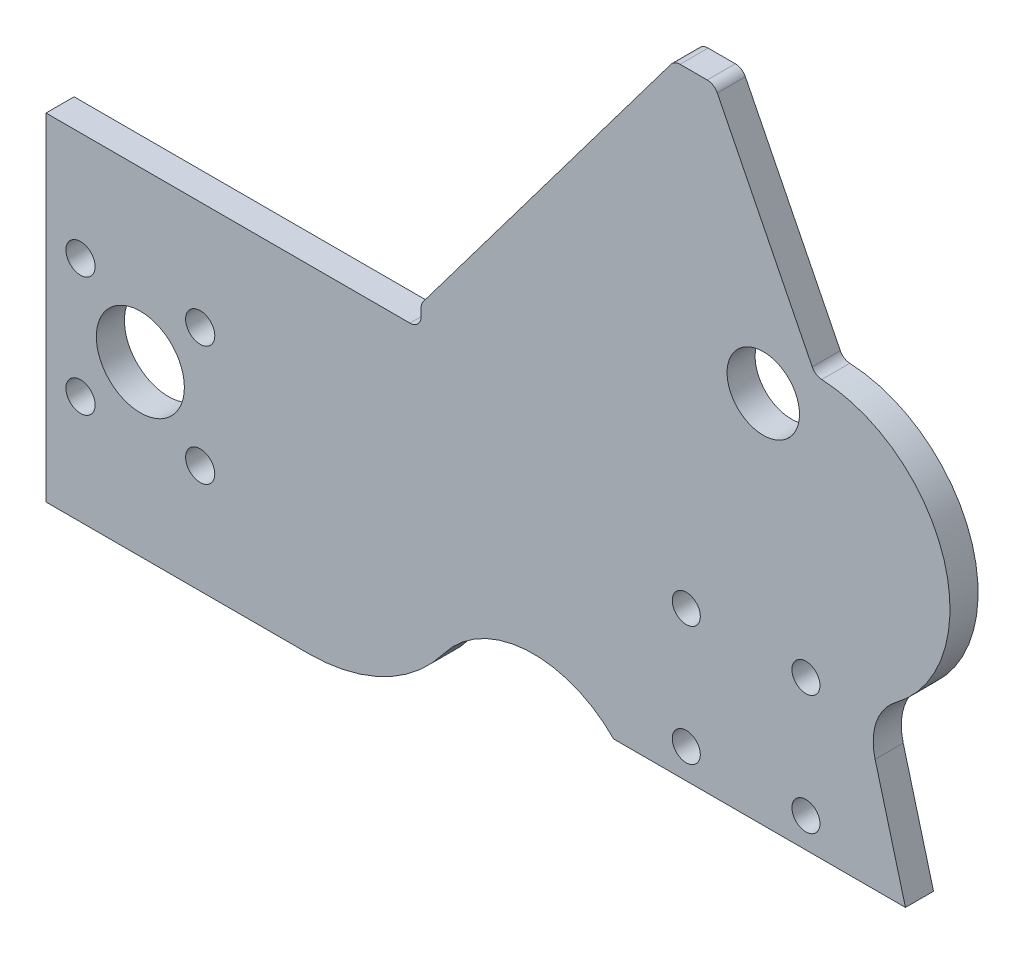
SolidWorks part; units mm, degrees
ref_plane "Front Plane" through (0, 0, 0) normal (0, 0, 1) x (1, 0, 0)
ref_plane "Top Plane" through (0, 0, 0) normal (0, 1, 0) x (1, 0, 0)
ref_plane "Right Plane" through (0, 0, 0) normal (1, 0, 0) x (0, 0, -1)
sketch "Sketch1" plane through (0, 0, 0) normal (0, 0, 1) x (1, 0, 0)
  line L0 (0, 0) -> (107.95, 0)
  line L3 (0, 38.1) -> (0, 25.4)
  line L4 (95.3675, 55.88) -> (0, 38.1)
  line L5 (0, 19.05) -> (100.2273, 19.05) construction
  line L6 (19.05, 19.05) -> (19.05, 28.62) construction
  line L7 (19.05, 19.05) -> (25.817, 25.817) construction
  line L8 (107.95, 0) -> (100.9363, 26.1756)
  line L10 (0, 12.7) -> (0, 0)
  line L11 (0, 25.4) -> (-7.62, 25.4)
  line L13 (0, 12.7) -> (-7.62, 12.7)
  line L14 (-7.62, 25.4) -> (-7.62, 12.7)
  line L15 (100.9363, 26.1756) -> (100.8688, 26.4276)
  arc A0 (100.8688, 26.4276) -> (95.3675, 55.88) centre (95.3675, 40.64) ccw
  circle A1 centre (95.3675, 40.64) radius 4.0957 construction
  circle A2 centre (19.05, 19.05) radius 9.57 construction
  circle A3 centre (25.817, 25.817) radius 1.651
  circle A4 centre (25.817, 12.283) radius 1.651
  circle A7 centre (12.283, 12.283) radius 1.651 [skipped]
  circle A8 centre (12.283, 25.817) radius 1.651 [skipped]
  point P26 (19.05, 19.05)
  dimension "D1" = 8.1915
  dimension "D5" = 15.24
  dimension "D4" = 19.14
  dimension "D7" = 3.302
  dimension "D11" = 97.0107
  dimension "D2" = 38.1
  dimension "D3" = 40.64
  dimension "D6" = 107.95
  dimension "D8" = 45
  dimension "D9" = 4
  dimension "D10" = 19.05
  dimension "D12" = 75
  dimension "D14" = 12.7
  dimension "D15" = 12.7
  dimension "D16" = 7.62
extrude "Boss-Extrude1" add sketch "Sketch1" along normal blind 3.175
sketch "Sketch2" plane through (0, 0, 3.175) normal (0, 0, 1) x (1, 0, 0)
  circle A0 centre (95.3675, 40.64) radius 38.1 construction
  point P3 (0, 0)
sketch "Sketch6" plane through (0, 0, 3.175) normal (0, 0, 1) x (1, 0, 0)
  line L0 (0, 0) -> (107.95, 0) construction
  line L1 (50.8, 0) -> (76.2, 0)
  arc A0 (76.2, 0) -> (50.8, 0) centre (63.5, 0) ccw
  dimension "D1" = 25.4
  dimension "D2" = 31.75
extrude "Cut-Extrude2" cut sketch "Sketch6" against normal blind 6.35
sketch "Sketch7" plane through (0, 0, 3.175) normal (0, 0, 1) x (1, 0, 0)
  line L0 (12.283, 25.817) -> (25.817, 12.283) construction
  line L1 (12.283, 12.283) -> (25.817, 25.817) construction
  circle A0 centre (19.05, 19.05) radius 4.9784
  circle A2 centre (80.7829, 12.2536) radius 1.5875
  circle A3 centre (94.316, 12.2536) radius 1.5875
  circle A4 centre (80.7829, 25.7876) radius 1.5875
  circle A5 centre (94.316, 25.7876) radius 1.5875
  point P10 (0, 0)
  point P11 (0, 0)
  point P20 (0, 0)
  dimension "D1" = 9.9568
extrude "Cut-Extrude3" cut sketch "Sketch7" against normal through all
fillet "Fillet1" radius 6.35 1 edges at (100.8688, 26.4276, 1.5875)
sketch "Sketch8" plane through (0, 0, 3.175) normal (0, 0, 1) x (1, 0, 0)
  line L1 (0, 38.1) -> (50.8, 38.1)
  line L2 (0, 38.1) -> (0, 50.8)
  line L3 (0, 50.8) -> (50.8, 50.8)
  line L4 (50.8, 38.1) -> (50.8, 50.8)
  dimension "D1" = 50.8
  dimension "D2" = 12.7
extrude "Cut-Extrude4" cut sketch "Sketch8" against normal blind 50.8
sketch "Sketch9" plane through (0, 0, 3.175) normal (0, 0, 1) x (1, 0, 0)
  line L3 (50.8, 40.64) -> (57.15, 40.64)
  line L5 (57.15, 40.64) -> (50.8, 40.64)
  line L6 (57.15, 40.64) -> (57.15, 50.8)
  line L7 (57.15, 50.8) -> (50.8, 50.8)
  line L8 (50.8, 40.64) -> (50.8, 50.8)
  line L9 (0, 38.1) -> (50.8, 38.1) construction
  line M8 (50.8, 47.571) -> (50.8, 38.1)
  line M21 (95.3675, 55.88) -> (50.8, 47.571)
  dimension "D1" = 10.16
  dimension "D2" = 2.54
  dimension "D3" = 6.35
extrude "Cut-Extrude5" cut sketch "Sketch9" against normal blind 19.304 contours L3 L6 M21 M8 region at (54.0583, 44.4092, 3.175)
fillet "Fillet6" radius 6.35 1 edges at (57.15, 40.64, 1.5875)
fillet "Fillet7" radius 6.35 1 edges at (57.15, 48.7549, 1.5875)
fillet "Fillet8" radius 19.05 1 edges at (50.8, 0, 1.5875)
sketch "Sketch12" plane through (0, 0, 3.175) normal (0, 0, 1) x (1, 0, 0)
  line L0 (107.95, 0) -> (146.812, 0) construction
  line L1 (8.0257, 45.4128) -> (80.6683, 75.7903) construction
  line L2 (95.3675, 40.64) -> (80.6683, 75.7903) construction
  line L3 (80.6683, 75.7903) -> (79.4434, 78.7195) construction
  line L4 (50.8, 40.64) -> (85.0271, 40.64)
  line L5 (85.0271, 40.64) -> (95.3675, 55.88)
  line L6 (50.8, 40.64) -> (79.4434, 78.7195)
  line L7 (79.4434, 78.7195) -> (83.9406, 78.7195)
  line L8 (83.9406, 78.7195) -> (95.3675, 55.88)
  circle A1 centre (19.05, 19.05) radius 28.575 construction
  circle A2 centre (95.3675, 40.64) radius 38.1 construction
  circle A3 centre (80.6683, 75.7903) radius 3.175 construction
  dimension "D1" = 38.862
extrude "Boss-Extrude2" add sketch "Sketch12" against normal blind 3.175
fillet "Fillet9" radius 24.13 rebuild error yes
sketch "Sketch13" plane through (0, 38.1, 0) normal (0, 1, 0) x (1, 0, 0)
  line L0 (8.382, -3.175) -> (8.382, 0)
  line L1 (0, -3.175) -> (50.8, -3.175) construction
  line L2 (0, 0) -> (50.8, 0) construction
  line L3 (0, -3.175) -> (0, 0) construction
  dimension "D1" = 8.382
extrude "Cut-Extrude6" cut sketch "Sketch13" against normal through all
sketch "Sketch14" plane through (0, 0, 3.175) normal (0, 0, 1) x (1, 0, 0)
  circle A0 centre (89.49, 51.1876) radius 4.0958
  circle A1 centre (94.316, 25.7876) radius 1.5875 construction
  dimension "D3" = 8.1915
  dimension "D1" = 4.826
  dimension "D2" = 25.4
extrude "Cut-Extrude7" cut sketch "Sketch14" against normal through all
sketch "Sketch17" plane through (0, 0, 3.175) normal (0, 0, 1) x (1, 0, 0)
  line L0 (76.2, 0) -> (107.95, 0) construction
  line L1 (64.0585, 8.89) -> (108.994, 8.89)
  line L2 (64.0585, 8.89) -> (64.0585, 0)
  line L3 (64.0585, 0) -> (108.994, 0)
  line L4 (108.994, 8.89) -> (108.994, 0)
  dimension "D1" = 8.89
extrude "Cut-Extrude10" cut sketch "Sketch17" against normal through all
sketch "Sketch18" plane through (0, 0, 3.175) normal (0, 0, 1) x (1, 0, 0)
  line L0 (19.05, 14.0716) -> (19.05, 24.0284) construction
  circle A0 centre (19.05, 19.05) radius 4.9784 construction
  circle A1 centre (25.817, 25.817) radius 1.651 construction
  circle A2 centre (25.817, 12.283) radius 1.651 construction
  circle A3 centre (12.283, 12.283) radius 1.651
  circle A4 centre (12.283, 25.817) radius 1.651
extrude "Cut-Extrude11" cut sketch "Sketch18" against normal through all
fillet "Fillet11" radius 1.27 5 edges at (95.3675, 55.88, 1.5875) (83.9406, 78.7195, 1.5875) (79.4434, 78.7195, 1.5875) (50.8, 38.1, 1.5875) (50.8, 40.64, 1.5875)
